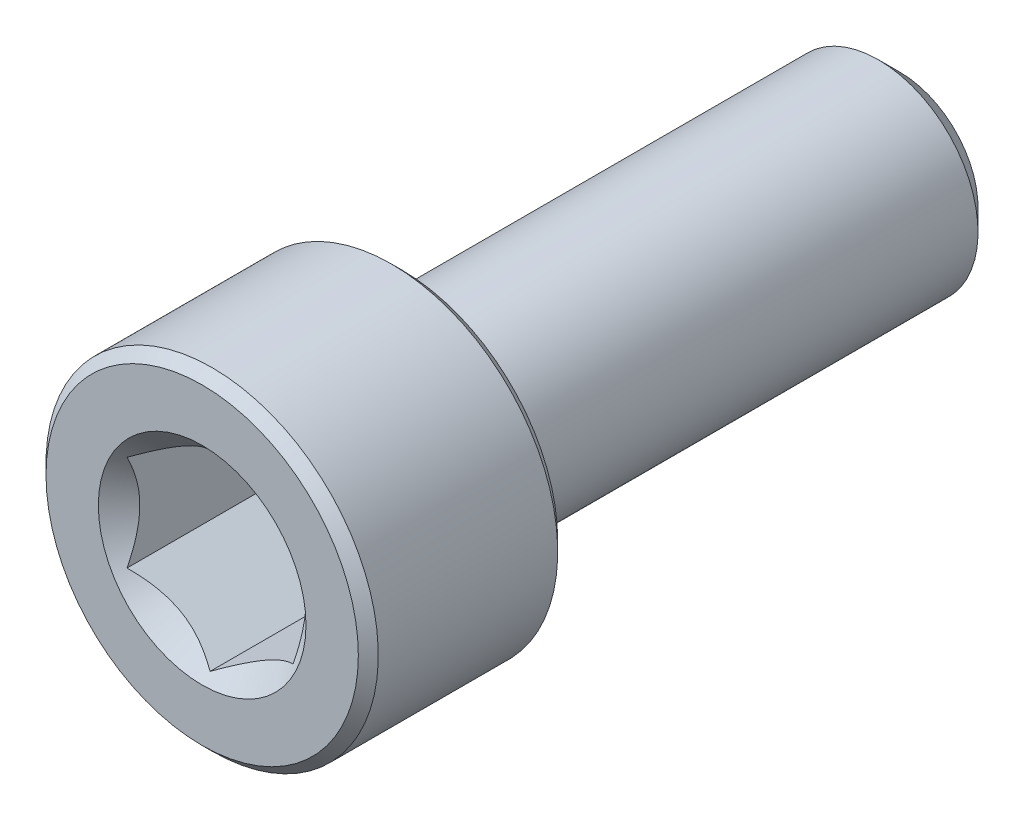
SolidWorks part; units mm, degrees
ref_plane "Front Plane" through (0, 0, 0) normal (0, 0, 1) x (1, 0, 0)
ref_plane "Top Plane" through (0, 0, 0) normal (0, 1, 0) x (1, 0, 0)
ref_plane "Right Plane" through (0, 0, 0) normal (1, 0, 0) x (0, 0, -1)
sketch "Sketch1" plane through (0, 0, 0) normal (1, 0, 0) x (0, 0, -1)
  line L0 (-10.5, 0) -> (10.5, 0) construction
  line L1 (10.5, 0) -> (10.5, 2.3505) construction
  line L2 (10.5, 2.3505) -> (9.8505, 3) construction
  line L3 (9.8505, 3) -> (9.75, 3) construction
  line L4 (9.75, 3) -> (-4.5, 3) construction
  line L5 (-4.5, 3) -> (-4.5, 5) construction
  line L6 (-4.5, 5) -> (-10.5, 5) construction
  line L7 (-10.5, 5) -> (-10.5, 0) construction
  line L8 (10.5, 2.3505) -> (10.5, 3) construction
  line L9 (10.4375, 3.1083) -> (10.9375, 2.2422) construction
  line L10 (10.9375, 2.2422) -> (11.4375, 3.1083) construction
  line L11 (11.4375, 3.1083) -> (10.4375, 3.1083) construction
  line L12 (10.9375, 3.1083) -> (10.9375, 3) construction
  line L13 (10.9375, 2.2422) -> (10.9375, 2.3505) construction
  line L14 (10.875, 2.3505) -> (11, 2.3505) construction
  line L15 (10.5, 3) -> (11.375, 3) construction
  line L16 (10.4687, 3.0541) -> (11.4063, 3.0541) construction
  line L17 (10.5, 0) -> (10.5, -3) construction
  line L18 (-4.8, 5) -> (-4.5, 4.7) construction
  line L19 (-10.2, 5) -> (-10.5, 4.7) construction
  line L20 (-4.5, 3) -> (-4.5, 0) construction
  line L21 (-4.5, 1.5) -> (0.5, 1.5) construction
  line L22 (0.5, 1.5) -> (5.5, 1.5) construction
  line L23 (5.5, 1.5) -> (10.5, 1.5) construction
  line L24 (0.5, 1.5) -> (0.5, 3) construction
  line L25 (0.5, 3) -> (0.5, 5) construction
  line L26 (5.5, 1.5) -> (5.5, 5) construction
  point P0 (-10.5, 2.5)
  point P3 (8, 3)
  point P4 (0, 0)
  point P18 (5.5, 3)
  point P22 (10.9375, 2.3505)
  point P24 (9.75, 3)
  point P25 (10.9375, 3)
  point P28 (10.9375, 3.0541)
  point P29 (8, -3)
  point P30 (0.5, 3)
  point P31 (-7.5, 5)
  point P37 (-5.55, 5)
  point P38 (-10.05, 5)
  point P45 (0.5, 1.5)
  point P46 (5.5, 1.5)
  dimension "D2" = 0.125
  dimension "D7" = 0.3
  dimension "D8" = 0.3
  dimension "D9" = 0.3
  dimension "D10" = 0.15
  dimension "D11" = 0.75
  dimension "Drive Size" = 5
  dimension "Head Diameter" = 10
  dimension "Head Height" = 6
  dimension "Thread Pitch" = 1
  dimension "Thread Size" = 6
  dimension "Length" = 15
  dimension "D12" = 0.75
  dimension "D4" = 2.5
  dimension "D3" = 45
sketch "Sketch2" plane through (0, 0, 0) normal (1, 0, 0) x (0, 0, -1)
  line L0 (-10.5, 0) -> (-10.5, 4.7)
  line L1 (-10.2, 5) -> (-4.8, 5)
  line L2 (-4.5, 4.7) -> (-4.5, 3.3)
  line L4 (9.8505, 3) -> (10.5, 2.3505)
  line L5 (10.5, 2.3505) -> (10.5, 0)
  line L6 (-4.5, 5) -> (-10.5, 5) construction
  line L7 (10.5, 0) -> (-10.5, 0)
  line L8 (-10.2, 5) -> (-10.5, 4.7) construction
  line L10 (-10.2, 5) -> (-10.5, 4.7)
  line L14 (-4.8, 5) -> (-4.5, 4.7) construction
  line L16 (-4.8, 5) -> (-4.5, 4.7)
  line L17 (-4.5, 3) -> (-4.5, 5) construction
  line L19 (-4.2, 3) -> (9.8505, 3)
  line L20 (9.75, 3) -> (-4.5, 3) construction
  arc A1 (-4.5, 3.3) -> (-4.2, 3) centre (-4.2, 3.3) ccw
  dimension "D3" = 0.3
revolve "Revolve1" add sketch "Sketch2" angle 360 about L7
sketch "Sketch3" plane through (0, 0, 10.5) normal (0, 0, 1) x (1, 0, 0)
  line L1 (2.5, -1.4434) -> (2.5, 1.4434)
  line L2 (2.5, 1.4434) -> (0, 2.8868)
  line L3 (0, 2.8868) -> (-2.5, 1.4434)
  line L4 (-2.5, 1.4434) -> (-2.5, -1.4434)
  line L5 (-2.5, -1.4434) -> (0, -2.8868)
  line L6 (0, -2.8868) -> (2.5, -1.4434)
  circle A0 centre (0, 0) radius 2.5 construction
  circle A1 centre (0, 0) radius 5 construction
  circle A2 centre (0, 0) radius 5 construction
  circle A3 centre (0, 0) radius 2.8868 construction
  point P13 (0, 0)
extrude "Cut-Extrude1" cut sketch "Sketch3" against normal offset from surface (5 mm away) 1 up to face at (0, 4.7, 4.5)
sketch "Sketch4" plane through (0, 0, 10.5) normal (0, 0, 1) x (1, 0, 0)
  circle A0 centre (0, 0) radius 3.125
  dimension "D1" = 6.25
extrude "Cut-Extrude2" cut sketch "Sketch4" against normal up to vertex (3 mm away) draft 45 up to point (0, 5, 7.5)
sketch "Sketch11" plane through (0, 0, 0) normal (1, 0, 0) x (0, 0, -1)
  line L0 (-10.5, 0) -> (10.5, 0) construction
  line L1 (-10.5, 0) -> (10.5, 0) construction
  line L2 (-1.6875, 0) -> (-1.6875, 3) construction
  line L3 (9.75, 3) -> (-4.5, 3) construction
  line L4 (7.6875, 0) -> (7.6875, 3) construction
  line L6 (10.5, 2.3505) -> (10.5, 3) construction
  point P2 (-1.6875, 0)
  point P3 (7.6875, 0)
  dimension "D1" = 2.8125
  dimension "D2" = 2.8125
sketch "Sketch6" [suppressed] plane through (0, 0, -10.5) normal (0, 0, -1) x (-1, 0, 0)
  circle A0 centre (0, 0) radius 3
curve "Helix/Spiral1" [suppressed] pitch 1 height 16 turns 16
sketch "Sketch10" [suppressed] plane through (0, 0, 0) normal (1, 0, 0) x (0, 0, -1)
  line L0 (-4.2, -5) -> (-4.2, 5)
  line L5 (-10.5, 0) -> (10.5, 0) construction
  line L6 (-4.2, 3) -> (-4.2, -3) construction
  point P3 (-4.2, 0)
split "Split1" [suppressed] bodies to split 106
sketch "Sketch7" [suppressed] plane through (0, 0, 0) normal (1, 0, 0) x (0, 0, -1)
  line L0 (10.4687, 3.0541) -> (11.4063, 3.0541)
  line L1 (11.4063, 3.0541) -> (11, 2.3505)
  line L2 (11, 2.3505) -> (10.875, 2.3505)
  line L3 (10.875, 2.3505) -> (10.4687, 3.0541)
sweep "Cut-Sweep1" [suppressed] cut profiles "Sketch7" path "Helix/Spiral1"
sketch "Sketch8" [suppressed] plane through (0, 0, 0) normal (1, 0, 0) x (0, 0, -1)
  line L0 (-4.5, 0) -> (-4.5, 3)
  line L1 (-4.2, -3) -> (-4.2, 3) construction
  line L2 (-4.5, 3) -> (-4.2, 3)
  line L4 (-4.2, 3) -> (-2.4679, 0)
  line L5 (-2.4679, 0) -> (-4.5, 0)
  line L6 (9.75, 3) -> (-4.5, 3) construction
  line L7 (-10.5, 0) -> (10.5, 0) construction
  dimension "D1" = 60
revolve "Revolve2" [suppressed] add sketch "Sketch8" angle 360 about L5
ref_plane "Plane1" [suppressed] through (0, 0, 10.5) normal (0, 0, 1) x (1, 0, 0)
sketch "Sketch12" [suppressed] plane through (0, 0, 10.5) normal (0, 0, 1) x (1, 0, 0)
  line L0 (0, 0) -> (0.1745, 4.997) construction
  line L1 (0, 0) -> (-0.1745, 4.997) construction
  line L2 (0, 4.875) -> (0, 5.125) construction
  line L3 (-0.3025, 5.125) -> (0.3025, 5.125)
  line L4 (-0.3025, 5.125) -> (-0.0897, 4.9122)
  line L5 (0.0897, 4.9122) -> (0.3025, 5.125)
  circle A0 centre (0, 0) radius 5 construction
  arc A1 (-0.0897, 4.9122) -> (0.0897, 4.9122) centre (0, 5.0019) ccw
  point P9 (0, 5.125)
  point P13 (0, 5)
  dimension "D2" = 0.125
  dimension "D1" = 4
extrude "Cut-Extrude3" [suppressed] cut sketch "Sketch12" against normal blind 4.8
pattern_circular "CirPattern1" [suppressed] count 72 over 360 about axis through (0, 0, 10.5) along (0, 0, -1) of bodies 118
equation "\"D2@Sketch1\" = \"Thread Pitch@Sketch1\" / 8"
equation "\"D4@Helix/Spiral1\" = \"Thread Pitch@Sketch1\""
equation "\"D7@Sketch1\" = \"Head Height@Sketch1\" * .05"
equation "\"D8@Sketch1\"=\"D7@Sketch1\""
equation "\"D9@Sketch1\"=\"D7@Sketch1\""
equation "\"D10@Sketch1\"=\"D7@Sketch1\"/2"
equation "\"D11@Sketch1\"=\"D10@Sketch1\"*5"
equation "\"D4@Sketch1\"=\"Thread Pitch@Sketch1\"*2.5"
equation "\"D12@Sketch1\"=\"Thread Pitch@Sketch1\"*.75"
equation "\"D3@Helix/Spiral1\"=\"Length@Sketch1\"+\"Thread Pitch@Sketch1\""
equation "\"D3@Sketch2\" = \"Thread Size@Sketch1\" * 0.05"
equation "\"D1@Sketch11\"=\"Length@Sketch1\"*0.1875"
equation "\"D2@Sketch11\"=\"D1@Sketch11\""
equation "\"D2@Sketch12\"=\"Head Diameter@Sketch1\"*.0125"
equation "\"D1@Cut-Extrude3\"=\"Head Height@Sketch1\"*.8"
equation "\"D1@CirPattern1\"=\"D3@CirPattern1\"/(1.25*\"D1@Sketch12\")"
equation "\"D1@Sketch4\"=\"Drive Size@Sketch1\"*1.25"
